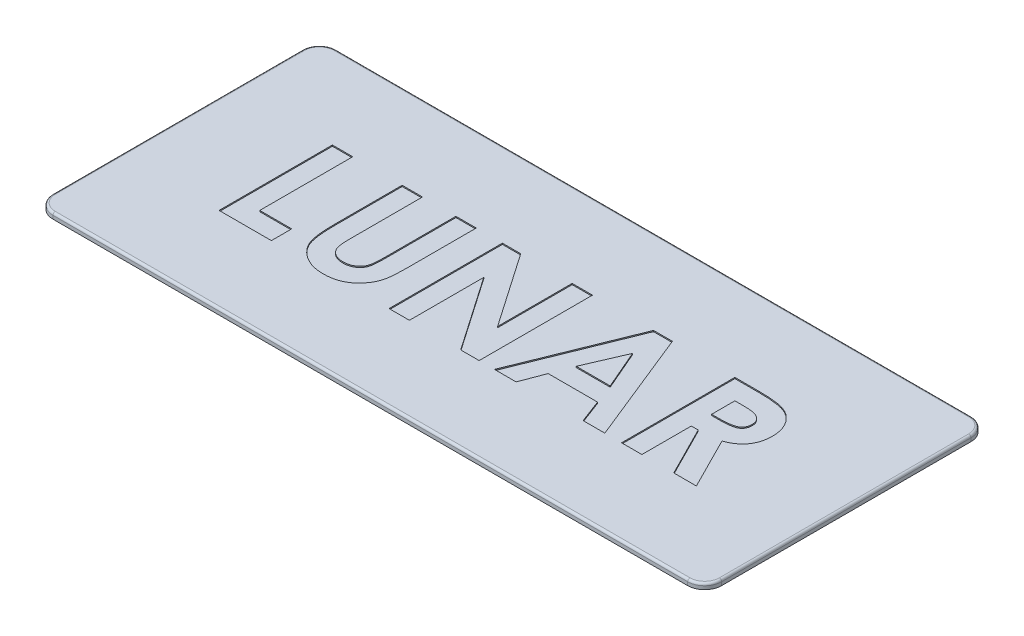
SolidWorks part; units mm, degrees
material "201 Annealed Stainless Steel (SS)"
ref_plane "Front Plane" through (0, 0, 0) normal (0, 0, 1) x (1, 0, 0)
ref_plane "Top Plane" through (0, 0, 0) normal (0, 1, 0) x (1, 0, 0)
ref_plane "Right Plane" through (0, 0, 0) normal (1, 0, 0) x (0, 0, -1)
sketch "Sketch1" plane through (0, 0, 0) normal (0, 1, 0) x (1, 0, 0)
  line L1 (-147.5, 62.5) -> (147.5, 62.5)
  line L2 (-147.5, 62.5) -> (-147.5, -62.5)
  line L3 (-147.5, -62.5) -> (147.5, -62.5)
  line L4 (147.5, 62.5) -> (147.5, -62.5)
  line L5 (-147.5, 62.5) -> (147.5, -62.5) construction
  line L6 (-147.5, -62.5) -> (147.5, 62.5) construction
  point P0 (0, 0)
  dimension "D1" = 295
  dimension "D2" = 125
extrude "Boss-Extrude1" add sketch "Sketch1" along normal blind 2.5
fillet "Fillet1" radius 7.5 4 edges at (147.5, 1.25, 62.5) (-147.5, 1.25, 62.5) (147.5, 1.25, -62.5) (-147.5, 1.25, -62.5)
fillet "Fillet2" radius 1 8 edges at (145.3033, 2.5, -60.3033) (147.5, 2.5, 0) (145.3033, 2.5, 60.3033) (0, 2.5, 62.5) (-145.3033, 2.5, 60.3033) (-147.5, 2.5, 0) (-145.3033, 2.5, -60.3033) (0, 2.5, -62.5)
sketch "Sketch3" plane through (0, 2.5, 0) normal (0, 1, 0) x (1, 0, 0)
  line L1 (-110, -25) -> (110, -25) construction
  line L2 (-110, -25) -> (-110, 25) construction
  line L3 (-110, 25) -> (110, 25) construction
  line L4 (110, -25) -> (110, 25) construction
  text T0 "LUNAR" font "Century Gothic" height 50
  point P4 (-110, 0)
  point P6 (0, 25)
  dimension "D1" = 220
  dimension "D2" = 50
extrude "Cut-Extrude3" cut sketch "Sketch3" against normal blind 0.5
